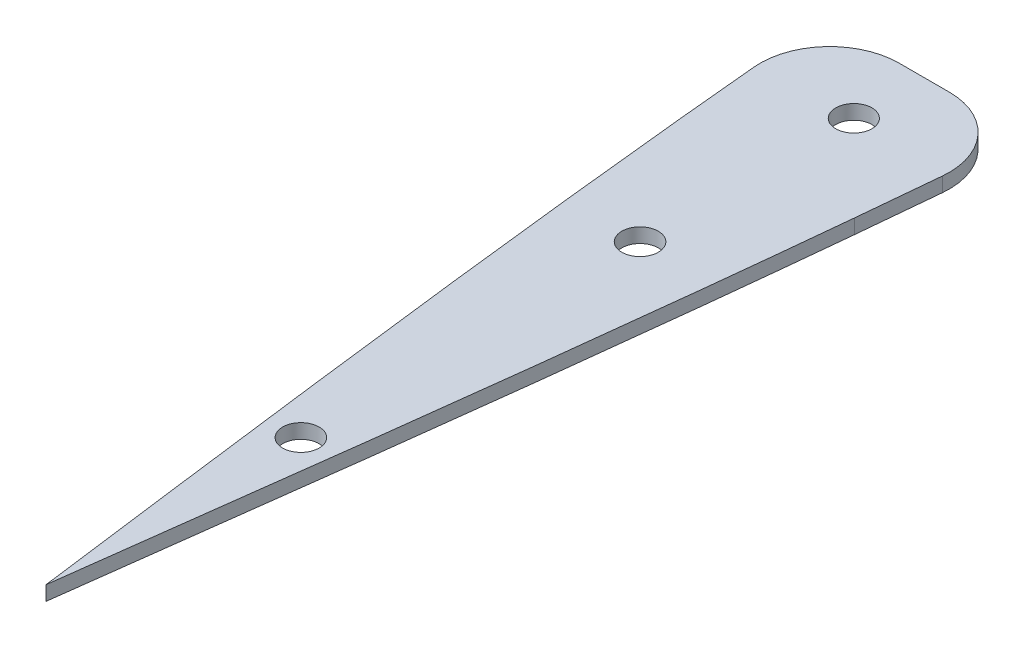
SolidWorks part; units mm, degrees
material "Balsa"
ref_plane "Front Plane" through (0, 0, 0) normal (0, 0, 1) x (1, 0, 0)
ref_plane "Top Plane" through (0, 0, 0) normal (0, 1, 0) x (1, 0, 0)
ref_plane "Right Plane" through (0, 0, 0) normal (1, 0, 0) x (0, 0, -1)
sketch "Sketch1" plane through (0, 0, 0) normal (0, 1, 0) x (1, 0, 0)
  line L0 (1.1081, 1.7265) -> (-45.0799, 1.7265) construction
  line L1 (-45.0799, 1.7265) -> (-45.0799, -11.2275) construction
  line L2 (-45.0799, -11.2275) -> (43.7517, -11.2275) construction
  line L3 (1.1081, 103.3269) -> (1.1081, -99.8738) construction
  line L4 (-45.0799, -11.2275) -> (-45.0799, -20.7525) construction
  line L5 (-28.2049, 1.7265) -> (-28.2049, -3.6075) construction
  line L6 (-9.9553, -3.6075) -> (-6.7697, -3.6075)
  line L7 (-28.2049, -3.6075) -> (-9.9553, -3.6075) construction
  line L8 (-6.7697, -3.6075) -> (1.1081, -3.6075) construction
  line L9 (8.9859, -3.6075) -> (12.1715, -3.6075)
  line L10 (12.1715, -3.6075) -> (18.1346, -3.6075) construction
  line L11 (12.1715, -3.6075) -> (18.1346, -3.6075) construction
  line L12 (18.1346, -3.6075) -> (29.3788, -3.6075) construction
  line L13 (1.1081, -3.6075) -> (8.9859, -3.6075) construction
  line L14 (-6.7697, -3.6075) -> (8.9859, -3.6075)
  circle A0 centre (1.1081, -11.3265) radius 1.9844 construction
  circle A1 centre (1.1081, -11.3265) radius 1.9844
  spline S0 degree 3 poles (1.1081, -99.8738) (4.5273, -73.5318) (7.9866, -47.1872) (10.6029, -20.7525) knots 0 0 0 0 0.38497 0.38497 0.38497 0.38497
  spline S3 degree 3 poles (1.1081, -99.8738) (-2.3112, -73.5318) (-5.7704, -47.1872) (-8.3867, -20.7525) knots 0 0 0 0 0.38497 0.38497 0.38497 0.38497
  spline S4 degree 3 poles (10.6029, -20.7525) (11.1, -15.7302) (11.6306, -10.016) (12.114, -4.2968) (12.1715, -3.6075) knots 0.38497 0.38497 0.38497 0.38497 0.458109 0.468132 0.468132 0.468132 0.468132
  spline S5 degree 3 poles (-8.3867, -20.7525) (-8.8838, -15.7302) (-9.4144, -10.016) (-9.8978, -4.2968) (-9.9553, -3.6075) knots 0.38497 0.38497 0.38497 0.38497 0.458109 0.468132 0.468132 0.468132 0.468132
  spline S8 degree 3 poles (12.1715, -3.6075) (12.8364, 4.367) (14.1908, 23.6726) (14.0058, 48.0803) (13.0188, 67.5796) (11.3266, 78.9472) (9.5869, 86.9693) (8.1237, 93.6397) (6.4505, 97.563) (4.8164, 101.3994) (2.3437, 102.5279) (1.1081, 103.3269) knots 0.468132 0.468132 0.468132 0.468132 0.584075 0.748482 0.821537 0.866809 0.914778 0.94069 0.965303 0.976863 1 1 1 1 construction
  spline S9 degree 3 poles (1.1081, 99.6196) (1.2739, 99.518) (1.6209, 99.2976) (2.0134, 99.0137) (2.3095, 98.7539) (2.4667, 98.5788) (2.6076, 98.3713) (2.8163, 97.9774) (3.0534, 97.4394) (3.4327, 96.5453) (3.8774, 95.496) (4.541, 93.8448) (5.2023, 91.9048) (5.8236, 89.3366) (6.4213, 86.5662) (7.0145, 83.8293) (7.767, 80.1951) (8.6007, 75.6781) (9.6391, 68.4081) (10.3034, 59.2354) (10.6788, 47.9926) (10.8555, 36.7918) (10.7415, 25.5951) (10.3009, 14.4244) (9.6564, 4.6878) (9.1767, -1.3266) (8.9859, -3.6075) knots 0.118744 0.118744 0.118744 0.118744 0.122149 0.125554 0.12896 0.132365 0.13577 0.139175 0.142581 0.145986 0.152796 0.159607 0.173228 0.186849 0.20047 0.214091 0.227711 0.254953 0.282195 0.336679 0.391163 0.445646 0.50013 0.554614 0.609098 0.642376 0.642376 0.642376 0.642376 construction
  spline S10 degree 3 poles (-7.1984, 1.7265) (-7.237, 2.2289) (-7.5577, 6.4638) (-8.0847, 14.4244) (-8.5253, 25.5951) (-8.6393, 36.7918) (-8.4626, 47.9926) (-8.0872, 59.2354) (-7.4229, 68.4081) (-6.3845, 75.6781) (-5.5508, 80.1951) (-4.7983, 83.8293) (-4.2051, 86.5662) (-3.6074, 89.3366) (-2.9861, 91.9048) (-2.3248, 93.8448) (-1.6612, 95.496) (-1.2165, 96.5453) (-0.8372, 97.4394) (-0.6001, 97.9774) (-0.3914, 98.3713) (-0.2505, 98.5788) (-0.0933, 98.7539) (0.2028, 99.0137) (0.5953, 99.2976) (0.9423, 99.518) (1.1081, 99.6196) knots 0.492798 0.492798 0.492798 0.492798 0.50013 0.554614 0.609098 0.663581 0.718065 0.772549 0.827033 0.854275 0.881516 0.895137 0.908758 0.922379 0.936 0.949621 0.956432 0.963242 0.966647 0.970053 0.973458 0.976863 0.980268 0.983674 0.987079 0.990484 0.990484 0.990484 0.990484 construction
  spline S11 degree 3 poles (-10.3826, 1.7265) (-10.8572, 7.9268) (-11.9611, 25.4575) (-11.7896, 48.0803) (-10.8026, 67.5796) (-9.1104, 78.9472) (-7.3707, 86.9693) (-5.9075, 93.6397) (-4.2343, 97.563) (-2.6002, 101.3994) (-0.1276, 102.5279) (1.1081, 103.3269) knots 0.493976 0.493976 0.493976 0.493976 0.584075 0.748482 0.821537 0.866809 0.914778 0.94069 0.965303 0.976863 1 1 1 1 construction
  spline S12 degree 3 poles (-9.9553, -3.6075) (-10.1035, -1.8299) (-10.2465, -0.0519) (-10.3826, 1.7265) knots 0.468132 0.468132 0.468132 0.468132 0.493976 0.493976 0.493976 0.493976 construction
  spline S13 degree 3 poles (-6.7697, -3.6075) (-6.9185, -1.8292) (-7.0618, -0.0511) (-7.1984, 1.7265) knots 0.466852 0.466852 0.466852 0.466852 0.492798 0.492798 0.492798 0.492798 construction
  dimension "D4" = 3.9688
  dimension "D1" = 12.954
  dimension "D2" = 9.525
  dimension "D3" = 5.334
extrude "Boss-Extrude1" add sketch "Sketch1" along normal blind 169.8727
sketch "Sketch2" plane through (0, 169.8727, 0) normal (0, 1, 0) x (1, 0, 0)
  line L1 (-9.9553, -3.6075) -> (25.8085, -3.6075)
  line L2 (-9.9553, -3.6075) -> (-9.9553, -26.3125)
  line L3 (-9.9553, -26.3125) -> (25.8085, -26.3125)
  line L4 (25.8085, -3.6075) -> (25.8085, -26.3125)
  circle A0 centre (1.1081, -11.3265) radius 1.9844 construction
  dimension "D1" = 14.986
extrude "Cut-Extrude1" cut sketch "Sketch2" against normal blind 23.0581
extrude "Cut-Extrude2" cut sketch "Sketch2<2>" along normal blind 23.0581 from surface starting at face at (-1.1046, 0, 29.7187)
sketch "Sketch2<2>" plane through (0, 169.8727, 0) normal (0, 1, 0) x (1, 0, 0) same geometry as "Sketch2"
fillet "Fillet1" radius 7.62 6 edges at (-7.8242, 11.5291, 26.3125) (10.0403, 11.5291, 26.3125) (12.1715, 84.9363, 3.6075) (-7.8242, 158.3436, 26.3125) (10.0403, 158.3436, 26.3125)
sketch "Sketch6" plane through (0, 0, 0) normal (0, -1, 0) x (1, 0, 0)
  line L0 (1.1081, 3.6075) -> (1.1081, 99.8738) construction
  line L1 (-1.6395, 3.6075) -> (3.8557, 3.6075) construction
  line L2 (-6.9254, 34.7606) -> (9.1416, 34.7606) construction
  circle A0 centre (1.1081, 71.9338) radius 2
  circle A1 centre (1.1081, 34.7606) radius 2
  dimension "D1" = 4
  dimension "D2" = 27.94
extrude "Cut-Extrude3" cut sketch "Sketch6" against normal through all both and the other way through all
sketch "Sketch7" plane through (0, 0, 0) normal (1, 0, 0) x (0, 0, -1)
  line L0 (-3.6075, 146.8145) -> (-3.6075, 23.0581) construction
  line L1 (-99.8738, 0) -> (-3.6075, 0)
  line L2 (-99.8738, 0) -> (-99.8738, 127.9186)
  line L3 (-99.8738, 127.9186) -> (-3.6075, 127.9186)
  line L4 (-3.6075, 0) -> (-3.6075, 127.9186)
  line L5 (-11.9209, 146.8145) -> (-20.7525, 146.8145) construction
  line L6 (-99.8738, 169.8727) -> (-3.6075, 169.8727)
  line L7 (-99.8738, 169.8727) -> (-99.8738, 129.5061)
  line L8 (-99.8738, 129.5061) -> (-3.6075, 129.5061)
  line L9 (-3.6075, 169.8727) -> (-3.6075, 129.5061)
  dimension "D1" = 17.3084
  dimension "D2" = 1.5875
extrude "Cut-Extrude4" cut sketch "Sketch7" against normal through all both and the other way through all
